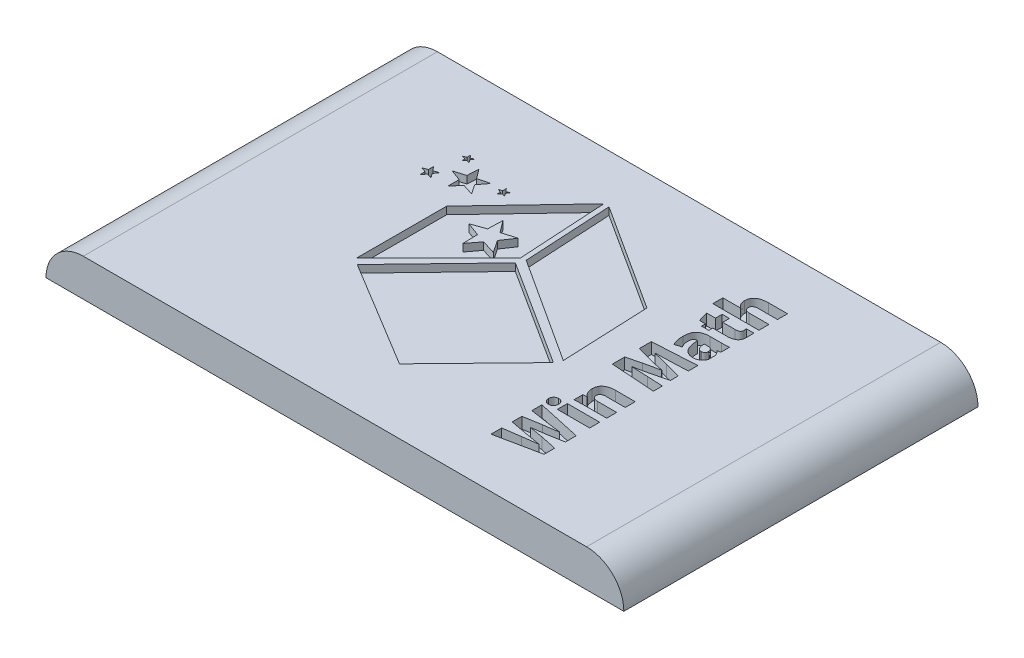
SolidWorks part; units mm, degrees
ref_plane "Front Plane" through (0, 0, 0) normal (0, 0, 1) x (1, 0, 0)
ref_plane "Top Plane" through (0, 0, 0) normal (0, 1, 0) x (1, 0, 0)
ref_plane "Right Plane" through (0, 0, 0) normal (1, 0, 0) x (0, 0, -1)
sketch "Sketch1" plane through (0, 0, 0) normal (0, 1, 0) x (1, 0, 0)
  line L1 (0, 0) -> (155, 0)
  line L2 (0, 0) -> (0, 95)
  line L3 (0, 95) -> (155, 95)
  line L4 (155, 0) -> (155, 95)
  dimension "D1" = 95
  dimension "D2" = 155
extrude "Boss-Extrude1" add sketch "Sketch1" along normal blind 10
fillet "Fillet1" radius 10 2 edges at (0, 10, -47.5) (155, 10, -47.5)
shell "Shell2" thickness 4 removed face at (77.5, 0, -47.5)
sketch "Sketch3" plane through (0, 10, 0) normal (0, 1, 0) x (1, 0, 0)
  line L0 (47.1109, 60.3769) -> (47.0833, 36.2437)
  line L1 (47.0833, 36.2437) -> (69.0367, 58.2599)
  line L2 (69.0367, 58.2599) -> (67.6381, 81.9832)
  line L3 (67.6381, 81.9832) -> (47.1109, 60.3769)
  line L4 (58.0076, 64.5969) -> (57.8826, 60.574)
  line L5 (57.8826, 60.574) -> (54.1743, 59.2566)
  line L6 (54.1743, 59.2566) -> (57.8661, 57.8917)
  line L7 (57.8661, 57.8917) -> (57.9418, 53.8673)
  line L8 (57.9418, 53.8673) -> (60.3485, 57.0467)
  line L9 (60.3485, 57.0467) -> (64.1037, 55.8769)
  line L10 (64.1037, 55.8769) -> (61.8991, 59.2068)
  line L11 (61.8991, 59.2068) -> (64.1443, 62.5081)
  line L12 (64.1443, 62.5081) -> (60.3751, 61.3868)
  line L13 (60.3751, 61.3868) -> (58.0076, 64.5969)
  line L14 (70.3473, 58.4621) -> (98.6174, 40.1514)
  line L15 (98.6174, 40.1514) -> (97.6168, 63.5776)
  line L16 (97.6168, 63.5776) -> (69.0367, 81.982)
  line L17 (69.0367, 81.982) -> (70.3473, 58.4621)
  line L18 (36.1479, 67.8344) -> (36.1422, 66.4292)
  line L19 (36.1422, 66.4292) -> (34.8275, 65.9323)
  line L20 (34.8275, 65.9323) -> (36.1624, 65.4928)
  line L21 (36.1624, 65.4928) -> (36.2285, 64.089)
  line L22 (36.2285, 64.089) -> (37.0591, 65.2226)
  line L23 (37.0591, 65.2226) -> (38.4147, 64.8518)
  line L24 (38.4147, 64.8518) -> (37.5931, 65.9921)
  line L25 (37.5931, 65.9921) -> (38.3648, 67.1665)
  line L26 (38.3648, 67.1665) -> (37.0264, 66.7376)
  line L27 (37.0264, 66.7376) -> (36.1479, 67.8344)
  line L28 (51.0281, 72.447) -> (51.027, 71.4893)
  line L29 (51.027, 71.4893) -> (50.1321, 71.148)
  line L30 (50.1321, 71.148) -> (51.0426, 70.8511)
  line L31 (51.0426, 70.8511) -> (51.0906, 69.8946)
  line L32 (51.0906, 69.8946) -> (51.6544, 70.6688)
  line L33 (51.6544, 70.6688) -> (52.5791, 70.4187)
  line L34 (52.5791, 70.4187) -> (52.0169, 71.1942)
  line L35 (52.0169, 71.1942) -> (52.5403, 71.9965)
  line L36 (52.5403, 71.9965) -> (51.6292, 71.7013)
  line L37 (51.6292, 71.7013) -> (51.0281, 72.447)
  line L38 (38.4638, 75.3981) -> (38.4901, 74.4758)
  line L39 (38.4901, 74.4758) -> (37.638, 74.1218)
  line L40 (37.638, 74.1218) -> (38.5233, 73.8618)
  line L41 (38.5233, 73.8618) -> (38.5967, 72.9421)
  line L42 (38.5967, 72.9421) -> (39.1174, 73.7036)
  line L43 (39.1174, 73.7036) -> (40.0149, 73.4891)
  line L44 (40.0149, 73.4891) -> (39.4515, 74.22)
  line L45 (39.4515, 74.22) -> (39.9328, 75.0072)
  line L46 (39.9328, 75.0072) -> (39.0638, 74.697)
  line L47 (39.0638, 74.697) -> (38.4638, 75.3981)
  line L48 (48.6785, 34.8084) -> (77.4183, 17.3974)
  line L49 (77.4183, 17.3974) -> (97.7621, 38.3361)
  line L50 (97.7621, 38.3361) -> (69.493, 56.4058)
  line L51 (69.493, 56.4058) -> (48.6785, 34.8084)
  line L52 (42.873, 73.2528) -> (42.6938, 70.2206)
  line L53 (42.6938, 70.2206) -> (39.6821, 69.2981)
  line L54 (39.6821, 69.2981) -> (42.6282, 68.1974)
  line L55 (42.6282, 68.1974) -> (42.6106, 65.1602)
  line L56 (42.6106, 65.1602) -> (44.6104, 67.5123)
  line L57 (44.6104, 67.5123) -> (47.6113, 66.5575)
  line L58 (47.6113, 66.5575) -> (45.9012, 69.1118)
  line L59 (45.9012, 69.1118) -> (47.7733, 71.5591)
  line L60 (47.7733, 71.5591) -> (44.7165, 70.7858)
  line L61 (44.7165, 70.7858) -> (42.873, 73.2528)
  spline S0 degree 3 poles (112.3162, 74.0035) (112.3162, 73.439) (112.3162, 72.8745) (112.3162, 72.31) knots 18 18 18 18 19 19 19 19
  spline S1 degree 3 poles (112.1249, 74.3129) (112.1938, 74.2134) (112.2528, 74.1068) (112.3162, 74.0035) knots 17 17 17 17 18 18 18 18
  spline S2 degree 3 poles (110.5374, 73.9138) (110.5459, 74.1404) (110.1829, 74.5507) (110.6633, 74.5671) (111.1436, 74.5834) (111.7302, 74.8835) (112.1249, 74.3129) knots 15 15 15 15 16 16 16 17 17 17 17
  spline S3 degree 3 poles (109.4304, 72.9149) (110.0624, 72.9344) (110.51, 73.187) (110.5374, 73.9138) knots 14 14 14 14 15 15 15 15
  spline S4 degree 3 poles (107.1794, 72.8956) (107.9262, 72.9505) (108.6805, 72.8917) (109.4304, 72.9149) knots 13 13 13 13 14 14 14 14
  spline S5 degree 3 poles (106.2942, 73.7451) (106.1518, 73.0011) (106.5134, 72.8465) (107.1794, 72.8956) knots 12 12 12 12 13 13 13 13
  spline S6 degree 3 poles (105.4432, 74.632) (106.1481, 74.6264) (106.4274, 74.442) (106.2942, 73.7451) knots 11 11 11 11 12 12 12 12
  spline S7 degree 3 poles (104.6003, 73.7348) (104.4834, 74.4138) (104.7173, 74.6378) (105.4432, 74.632) knots 10 10 10 10 11 11 11 11
  spline S8 degree 3 poles (103.8002, 72.8978) (104.4815, 72.8168) (104.7098, 73.0998) (104.6003, 73.7348) knots 9 9 9 9 10 10 10 10
  spline S9 degree 3 poles (102.3025, 72.9083) (102.8712, 72.9083) (103.3417, 72.9524) (103.8002, 72.8978) knots 8 8 8 8 9 9 9 9
  spline S10 degree 3 poles (102.6278, 71.762) (102.5888, 72.1199) (102.4324, 72.465) (102.3025, 72.9083) knots 7 7 7 7 8 8 8 8
  spline S11 degree 3 poles (104.0804, 70.6118) (103.1368, 70.4326) (102.7255, 70.8623) (102.6278, 71.762) knots 6 6 6 6 7 7 7 7
  spline S12 degree 3 poles (104.5957, 69.9056) (104.6247, 70.2676) (104.7022, 70.73) (104.0804, 70.6118) knots 5 5 5 5 6 6 6 6
  spline S13 degree 3 poles (105.162, 69.4172) (104.8053, 69.3444) (104.5596, 69.4567) (104.5957, 69.9056) knots 4 4 4 4 5 5 5 5
  spline S14 degree 3 poles (106.239, 69.7092) (106.2741, 69.1592) (105.5409, 69.4947) (105.162, 69.4172) knots 3 3 3 3 4 4 4 4
  spline S15 degree 3 poles (107.4693, 70.6148) (106.8556, 70.6087) (106.1666, 70.843) (106.239, 69.7092) knots 2 2 2 2 3 3 3 3
  spline S16 degree 3 poles (109.6276, 70.6122) (108.9089, 70.6355) (108.1888, 70.6217) (107.4693, 70.6148) knots 1 1 1 1 2 2 2 2
  spline S17 degree 3 poles (112.3162, 72.31) (111.8721, 71.028) (110.9158, 70.5701) (109.6276, 70.6122) knots 0 0 0 0 1 1 1 1
  spline S18 degree 3 poles (101.0336, 30.8311) (101.012, 31.0115) (101.0121, 31.3775) (101.0336, 31.5579) knots 4 4 4 4 5 5 5 5
  spline S19 degree 3 poles (102.4218, 29.9289) (101.7033, 29.7892) (101.1233, 30.0827) (101.0336, 30.8311) knots 3 3 3 3 4 4 4 4
  spline S20 degree 3 poles (103.3567, 31.1524) (103.3501, 30.5233) (103.0596, 30.0529) (102.4218, 29.9289) knots 2 2 2 2 3 3 3 3
  spline S21 degree 3 poles (102.4225, 32.4638) (103.1294, 32.3367) (103.3635, 31.8052) (103.3567, 31.1524) knots 1 1 1 1 2 2 2 2
  spline S22 degree 3 poles (101.0336, 31.5579) (101.1228, 32.3078) (101.7049, 32.5929) (102.4225, 32.4638) knots 0 0 0 0 1 1 1 1
  spline S23 degree 3 poles (103.3839, 17.0908) (105.4024, 17.5283) (107.4247, 17.9477) (109.4253, 18.3708) knots 17 17 17 17 18 18 18 18
  spline S24 degree 3 poles (101.579, 14.8015) (101.5551, 16.6817) (101.5349, 16.6901) (103.3839, 17.0908) knots 16 16 16 16 17 17 17 17
  spline S25 degree 3 poles (102.2542, 14.2833) (101.6623, 14.1186) (101.5858, 14.2574) (101.579, 14.8015) knots 15 15 15 15 16 16 16 16
  spline S26 degree 3 poles (110.2388, 16.3991) (107.5763, 15.6969) (104.9066, 15.0215) (102.2542, 14.2833) knots 14 14 14 14 15 15 15 15
  spline S27 degree 3 poles (112.1448, 18.8638) (112.1183, 16.9059) (112.1481, 16.9027) (110.2388, 16.3991) knots 13 13 13 13 14 14 14 14
  spline S28 degree 3 poles (111.3476, 19.8495) (111.9397, 19.7038) (112.1534, 19.4935) (112.1448, 18.8638) knots 12 12 12 12 13 13 13 13
  spline S29 degree 3 poles (104.6287, 21.6224) (106.9397, 21.0063) (109.1351, 20.3936) (111.3476, 19.8495) knots 11 11 11 11 12 12 12 12
  spline S30 degree 3 poles (110.2772, 23.0869) (108.4322, 22.6042) (106.5854, 22.1294) (104.6287, 21.6224) knots 10 10 10 10 11 11 11 11
  spline S31 degree 3 poles (112.1398, 25.6724) (112.2343, 23.6052) (112.2479, 23.6025) (110.2772, 23.0869) knots 9 9 9 9 10 10 10 10
  spline S32 degree 3 poles (111.6626, 26.3302) (112.0283, 26.2348) (112.1229, 26.0446) (112.1398, 25.6724) knots 8 8 8 8 9 9 9 9
  spline S33 degree 3 poles (101.5904, 28.9765) (105.011, 28.0762) (108.3354, 27.1977) (111.6626, 26.3302) knots 7 7 7 7 8 8 8 8
  spline S34 degree 3 poles (101.58, 27.6056) (101.6395, 28.0284) (101.5904, 28.4665) (101.5904, 28.9765) knots 6 6 6 6 7 7 7 7
  spline S35 degree 3 poles (102.5993, 26.3575) (101.7769, 26.4996) (101.4647, 26.7878) (101.58, 27.6056) knots 5 5 5 5 6 6 6 6
  spline S36 degree 3 poles (109.4363, 24.9636) (107.0496, 25.4595) (104.8353, 25.971) (102.5993, 26.3575) knots 4 4 4 4 5 5 5 5
  spline S37 degree 3 poles (103.4359, 23.5078) (105.3818, 23.9769) (107.3264, 24.4514) (109.4363, 24.9636) knots 3 3 3 3 4 4 4 4
  spline S38 degree 3 poles (101.5805, 21.0141) (101.4585, 23.0314) (101.4478, 23.0285) (103.4359, 23.5078) knots 2 2 2 2 3 3 3 3
  spline S39 degree 3 poles (102.0765, 20.3639) (101.7, 20.4638) (101.6029, 20.6435) (101.5805, 21.0141) knots 1 1 1 1 2 2 2 2
  spline S40 degree 3 poles (109.4253, 18.3708) (106.9688, 19.0401) (104.5258, 19.7142) (102.0765, 20.3639) knots 0 0 0 0 1 1 1 1
  spline S41 degree 3 poles (104.1541, 50.0484) (104.4099, 50.1937) (104.807, 50.0704) (105.1942, 50.0781) knots 23 23 23 23 24 24 24 24
  spline S42 degree 3 poles (104.6284, 50.2523) (104.4306, 50.188) (104.2333, 50.0814) (104.1541, 50.0484) knots 22 22 22 22 23 23 23 23
  spline S43 degree 3 poles (111.4571, 52.606) (109.1638, 51.8748) (106.9022, 51.0442) (104.6284, 50.2523) knots 21 21 21 21 22 22 22 22
  spline S44 degree 3 poles (112.1332, 53.9092) (112.1102, 53.3632) (112.2355, 52.8542) (111.4571, 52.606) knots 20 20 20 20 21 21 21 21
  spline S45 degree 3 poles (111.4136, 55.072) (112.1488, 54.9063) (112.1567, 54.4708) (112.1332, 53.9092) knots 19 19 19 19 20 20 20 20
  spline S46 degree 3 poles (108.8369, 55.9454) (109.6941, 55.6467) (110.5339, 55.2705) (111.4136, 55.072) knots 18 18 18 18 19 19 19 19
  spline S47 degree 3 poles (104.6493, 57.4043) (106.0452, 56.9181) (107.4412, 56.4319) (108.8369, 55.9454) knots 17 17 17 17 18 18 18 18
  spline S48 degree 3 poles (104.6883, 57.5987) (104.6754, 57.5341) (104.6624, 57.4692) (104.6493, 57.4043) knots 16 16 16 16 17 17 17 17
  spline S49 degree 3 poles (112.1442, 59.0497) (112.0997, 57.6) (112.1363, 57.5987) (110.6425, 57.5987) (108.6577, 57.5987) (106.6731, 57.5987) (104.6883, 57.5987) knots 14 14 14 14 15 15 15 16 16 16 16
  spline S50 degree 3 poles (111.2873, 59.9443) (112.0244, 59.9612) (112.165, 59.7245) (112.1442, 59.0497) knots 13 13 13 13 14 14 14 14
  spline S51 degree 3 poles (104.2342, 59.9145) (106.5851, 59.943) (108.9374, 59.8903) (111.2873, 59.9443) knots 12 12 12 12 13 13 13 13
  spline S52 degree 3 poles (101.7295, 59.733) (102.2215, 60.3085) (103.372, 59.904) (104.2342, 59.9145) knots 11 11 11 11 12 12 12 12
  spline S53 degree 3 poles (101.5783, 57.2807) (101.6437, 58.1186) (101.3062, 59.2375) (101.7295, 59.733) knots 10 10 10 10 11 11 11 11
  spline S54 degree 3 poles (102.2759, 56.2896) (101.7475, 56.4642) (101.5338, 56.7115) (101.5783, 57.2807) knots 9 9 9 9 10 10 10 10
  spline S55 degree 3 poles (109.093, 53.9639) (106.8433, 54.7357) (104.5664, 55.5333) (102.2759, 56.2896) knots 8 8 8 8 9 9 9 9
  spline S56 degree 3 poles (104.0484, 52.2386) (105.733, 52.8204) (107.4206, 53.3926) (109.093, 53.9639) knots 7 7 7 7 8 8 8 8
  spline S57 degree 3 poles (101.7385, 51.3251) (102.1888, 51.8865) (103.2509, 51.9632) (104.0484, 52.2386) knots 6 6 6 6 7 7 7 7
  spline S58 degree 3 poles (101.5805, 48.7731) (101.6626, 49.6393) (101.2518, 50.718) (101.7385, 51.3251) knots 5 5 5 5 6 6 6 6
  spline S59 degree 3 poles (102.4023, 47.9412) (101.7409, 47.9324) (101.518, 48.1149) (101.5805, 48.7731) knots 4 4 4 4 5 5 5 5
  spline S60 degree 3 poles (110.8665, 47.957) (108.0451, 47.957) (105.2232, 47.9785) (102.4023, 47.9412) knots 3 3 3 3 4 4 4 4
  spline S61 degree 3 poles (112.145, 49.2617) (112.1034, 47.9585) (112.144, 47.9571) (110.8665, 47.957) knots 2 2 2 2 3 3 3 3
  spline S62 degree 3 poles (111.307, 50.0877) (111.9605, 50.1009) (112.1663, 49.9308) (112.145, 49.2617) knots 1 1 1 1 2 2 2 2
  spline S63 degree 3 poles (105.1942, 50.0781) (107.2319, 50.0763) (109.2702, 50.0471) (111.307, 50.0877) knots 0 0 0 0 1 1 1 1
  spline S64 degree 3 poles (104.4141, 80.8549) (104.5146, 82.1147) (105.1697, 82.7689) (106.654, 83.0604) knots 14 14 14 14 15 15 15 15
  spline S65 degree 3 poles (105.3518, 78.5159) (104.6971, 79.1584) (104.3391, 79.9144) (104.4141, 80.8549) knots 13 13 13 13 14 14 14 14
  spline S66 degree 3 poles (105.3182, 78.1874) (105.7407, 78.2069) (105.6135, 78.3763) (105.3518, 78.5159) knots 12 12 12 12 13 13 13 13
  spline S67 degree 3 poles (101.0733, 75.9216) (100.8796, 78.1775) (100.8796, 78.1775) (103.0861, 78.1775) (103.8303, 78.1775) (104.5756, 78.153) (105.3182, 78.1874) knots 10 10 10 10 11 11 11 12 12 12 12
  spline S68 degree 3 poles (111.3175, 75.9029) (107.903, 75.9381) (104.4882, 75.9207) (101.0733, 75.9216) knots 9 9 9 9 10 10 10 10
  spline S69 degree 3 poles (112.1332, 76.7386) (112.2306, 76.0861) (111.9831, 75.8959) (111.3175, 75.9029) knots 8 8 8 8 9 9 9 9
  spline S70 degree 3 poles (112.1332, 77.395) (112.1018, 77.1804) (112.1012, 76.9532) (112.1332, 76.7386) knots 7 7 7 7 8 8 8 8
  spline S71 degree 3 poles (111.3287, 78.2416) (112.0082, 78.2535) (112.2262, 78.0334) (112.1332, 77.395) knots 6 6 6 6 7 7 7 7
  spline S72 degree 3 poles (107.3892, 78.3046) (108.6961, 78.1117) (110.0166, 78.2186) (111.3287, 78.2416) knots 5 5 5 5 6 6 6 6
  spline S73 degree 3 poles (106.215, 79.7438) (106.1609, 78.9437) (106.5922, 78.4224) (107.3892, 78.3046) knots 4 4 4 4 5 5 5 5
  spline S74 degree 3 poles (107.5362, 80.7968) (106.8534, 80.7727) (106.2673, 80.5215) (106.215, 79.7438) knots 3 3 3 3 4 4 4 4
  spline S75 degree 3 poles (109.9793, 80.8108) (109.1649, 80.8104) (108.3497, 80.8255) (107.5362, 80.7968) knots 2 2 2 2 3 3 3 3
  spline S76 degree 3 poles (112.1062, 83.0159) (112.1874, 80.8111) (112.1874, 80.8119) (109.9793, 80.8108) knots 1 1 1 1 2 2 2 2
  spline S77 degree 3 poles (106.654, 83.0604) (108.4714, 83.0457) (110.2888, 83.0308) (112.1062, 83.0159) knots 0 0 0 0 1 1 1 1
  spline S78 degree 3 poles (104.6008, 35.602) (104.5942, 36.2331) (104.4158, 37.0061) (105.678, 36.6475) knots 14 14 14 14 15 15 15 15
  spline S79 degree 3 poles (104.5966, 35.0382) (104.6254, 35.2218) (104.6026, 35.4138) (104.6008, 35.602) knots 13 13 13 13 14 14 14 14
  spline S80 degree 3 poles (105.3395, 34.3205) (104.7827, 34.3099) (104.5016, 34.4317) (104.5966, 35.0382) knots 12 12 12 12 13 13 13 13
  spline S81 degree 3 poles (112.1418, 35.8544) (112.1233, 34.333) (112.1505, 34.3327) (110.6078, 34.3327) (108.8516, 34.3327) (107.095, 34.3538) (105.3395, 34.3205) knots 10 10 10 10 11 11 11 12 12 12 12
  spline S82 degree 3 poles (111.3765, 36.6519) (112.0205, 36.6779) (112.149, 36.4437) (112.1418, 35.8544) knots 9 9 9 9 10 10 10 10
  spline S83 degree 3 poles (107.7091, 36.6628) (108.9297, 36.6066) (110.1557, 36.6026) (111.3765, 36.6519) knots 8 8 8 8 9 9 9 9
  spline S84 degree 3 poles (106.1999, 38.0294) (106.1821, 37.2943) (106.7898, 36.7052) (107.7091, 36.6628) knots 7 7 7 7 8 8 8 8
  spline S85 degree 3 poles (107.6693, 39.2727) (106.8997, 39.2311) (106.2229, 38.9732) (106.1999, 38.0294) knots 6 6 6 6 7 7 7 7
  spline S86 degree 3 poles (110.4904, 39.3001) (109.5497, 39.2987) (108.6074, 39.3235) (107.6693, 39.2727) knots 5 5 5 5 6 6 6 6
  spline S87 degree 3 poles (112.1363, 41.1729) (112.371, 39.4291) (112.2679, 39.3028) (110.4904, 39.3001) knots 4 4 4 4 5 5 5 5
  spline S88 degree 3 poles (111.6822, 41.6063) (112.0025, 41.6176) (112.094, 41.4859) (112.1363, 41.1729) knots 3 3 3 3 4 4 4 4
  spline S89 degree 3 poles (106.4245, 41.4787) (108.1671, 41.7607) (109.9297, 41.5443) (111.6822, 41.6063) knots 2 2 2 2 3 3 3 3
  spline S90 degree 3 poles (104.4599, 38.5103) (104.1324, 40.0226) (104.9022, 41.2325) (106.4245, 41.4787) knots 1 1 1 1 2 2 2 2
  spline S91 degree 3 poles (105.678, 36.6475) (104.9821, 37.2484) (104.6115, 37.8094) (104.4599, 38.5103) knots 0 0 0 0 1 1 1 1
  spline S92 degree 3 poles (106.1093, 32.3089) (106.8609, 32.3089) (107.6127, 32.3089) (108.3642, 32.3088) knots 6 6 6 6 7 7 7 7
  spline S93 degree 3 poles (104.5857, 30.7828) (104.6074, 32.3084) (104.5771, 32.3088) (106.1093, 32.3089) knots 5 5 5 5 6 6 6 6
  spline S94 degree 3 poles (105.3586, 29.9894) (104.725, 29.9733) (104.5773, 30.1792) (104.5857, 30.7828) knots 4 4 4 4 5 5 5 5
  spline S95 degree 3 poles (112.1415, 31.6289) (112.1556, 30.0042) (112.178, 30.0044) (110.526, 30.0044) (108.8034, 30.0044) (107.0801, 30.0332) (105.3586, 29.9894) knots 2 2 2 2 3 3 3 4 4 4 4
  spline S96 degree 3 poles (111.4645, 32.3203) (112.0101, 32.3418) (112.1369, 32.1477) (112.1415, 31.6289) knots 1 1 1 1 2 2 2 2
  spline S97 degree 3 poles (108.3642, 32.3088) (109.3979, 32.3086) (110.4325, 32.2798) (111.4645, 32.3203) knots 0 0 0 0 1 1 1 1
  spline S98 degree 3 poles (111.4373, 68.2591) (110.1234, 68.2286) (108.8078, 68.2683) (107.4936, 68.2444) knots 15 15 15 15 16 16 16 16
  spline S99 degree 3 poles (112.133, 67.5965) (112.2113, 68.158) (111.9445, 68.2711) (111.4373, 68.2591) knots 14 14 14 14 15 15 15 15
  spline S100 degree 3 poles (112.1301, 66.9401) (112.1181, 67.1584) (112.1029, 67.3817) (112.133, 67.5965) knots 13 13 13 13 14 14 14 14
  spline S101 degree 3 poles (111.1942, 66.0808) (112.2251, 65.7883) (112.1611, 66.3737) (112.1301, 66.9401) knots 12 12 12 12 13 13 13 13
  spline S102 degree 3 poles (112.3162, 64.5949) (111.9853, 65.0617) (111.7247, 65.5775) (111.1942, 66.0808) knots 11 11 11 11 12 12 12 12
  spline S103 degree 3 poles (112.3162, 63.0895) (112.3162, 63.5912) (112.3162, 64.0932) (112.3162, 64.5949) knots 10 10 10 10 11 11 11 11
  spline S104 degree 3 poles (109.6901, 61.4519) (110.8719, 61.2935) (111.64, 61.7723) (112.3162, 63.0895) knots 9 9 9 9 10 10 10 10
  spline S105 degree 3 poles (107.5555, 63.8176) (107.8334, 62.3093) (108.4666, 61.6158) (109.6901, 61.4519) knots 8 8 8 8 9 9 9 9
  spline S106 degree 3 poles (107.2955, 65.4852) (107.3993, 64.9327) (107.4537, 64.3707) (107.5555, 63.8176) knots 7 7 7 7 8 8 8 8
  spline S107 degree 3 poles (107.0656, 66.0385) (107.3453, 65.9728) (107.2591, 65.6795) (107.2955, 65.4852) knots 6 6 6 6 7 7 7 7
  spline S108 degree 3 poles (106.3903, 65.7822) (106.574, 65.9588) (106.8089, 66.0992) (107.0656, 66.0385) knots 5 5 5 5 6 6 6 6
  spline S109 degree 3 poles (106.0189, 64.3847) (105.9906, 64.8915) (105.9875, 65.3954) (106.3903, 65.7822) knots 4 4 4 4 5 5 5 5
  spline S110 degree 3 poles (106.6826, 62.2613) (106.4259, 62.9661) (106.0608, 63.6298) (106.0189, 64.3847) knots 3 3 3 3 4 4 4 4
  spline S111 degree 3 poles (104.5868, 63.6662) (104.8915, 62.0965) (104.9568, 62.0586) (106.6826, 62.2613) knots 2 2 2 2 3 3 3 3
  spline S112 degree 3 poles (104.4205, 65.0595) (104.4246, 64.5942) (104.4979, 64.1247) (104.5868, 63.6662) knots 1 1 1 1 2 2 2 2
  spline S113 degree 3 poles (107.4936, 68.2444) (105.4358, 68.2069) (104.4029, 67.1349) (104.4205, 65.0595) knots 0 0 0 0 1 1 1 1
  spline S114 degree 3 poles (108.9846, 66.0792) (109.8452, 66.1209) (110.6122, 65.513) (110.6554, 64.6919) knots 3 3 3 3 4 4 4 4
  spline S115 degree 3 poles (108.6052, 65.5365) (108.5486, 65.8447) (108.5517, 66.058) (108.9846, 66.0792) knots 2 2 2 2 3 3 3 3
  spline S116 degree 3 poles (109.8132, 63.5703) (109.076, 63.4828) (108.6888, 64.1318) (108.6052, 65.5365) knots 1 1 1 1 2 2 2 2
  spline S117 degree 3 poles (110.6554, 64.6919) (110.6875, 64.0804) (110.4584, 63.6467) (109.8132, 63.5703) knots 0 0 0 0 1 1 1 1
extrude "Cut-Extrude2" cut sketch "Sketch3" against normal blind 2 contours L2 L3 L0 L1 L13 L12 L11 L10 L9 L8 L7 L6 L5 L4 | L50 L51 L48 L49 | L16 L17 L14 L15 | L26 L27 L18 L19 L20 L21 L22 L23 L24 L25 | L46 L47 L38 L39 L40 L41 L42 L43 L44 L45 | L60 L61 L52 L53 L54 L55 L56 L57 L58 L59 | L36 L37 L28 L29 L30 L31 L32 L33 L34 L35 region at (57.7423, 10, -70.8306) region at (83.9146, 10, -61.0578) region at (36.7966, 10, -65.9748) region at (51.474, 10, -71.181) region at (38.9292, 10, -74.1916) region at (73.2779, 10, -36.7846) region at (44.1101, 10, -69.1656)
sketch "Sketch10" plane through (0, 10, 0) normal (0, 1, 0) x (1, 0, 0)
  line L0 (110.1325, 76.1337) -> (110.1345, 76.1026)
  line L1 (10, 0) -> (145, 0) construction
  line L2 (117.8303, 95) -> (117.8303, 0)
  line L3 (145, 95) -> (10, 95) construction
  line L4 (110.1345, 76.1026) -> (105.4552, 76.1026)
  line L5 (105.4552, 76.1026) -> (105.4552, 73.4158)
  line L6 (105.4552, 73.4158) -> (117.8214, 73.4158)
  line L7 (117.8214, 73.4158) -> (117.8214, 76.1026)
  line L8 (117.8214, 76.1026) -> (112.5347, 76.1026)
  line L9 (112.8304, 78.3957) -> (117.8214, 78.3979)
  line L10 (117.8214, 78.3979) -> (117.8214, 81.0847)
  line L11 (117.8214, 81.0847) -> (112.7429, 81.0847)
  line L12 (109.1674, 67.7279) -> (109.1674, 66.6671)
  line L13 (109.1674, 66.6671) -> (111.1199, 66.6671)
  line L14 (111.1199, 66.6671) -> (111.1199, 67.7279)
  line L15 (111.1199, 67.7279) -> (114.7821, 67.7279)
  line L16 (117.7725, 72.0924) -> (115.7681, 72.0786)
  line L17 (114.4363, 70.4021) -> (111.1199, 70.4029)
  line L18 (111.1199, 70.4029) -> (111.1199, 72.2016)
  line L19 (111.1199, 72.2016) -> (109.1674, 72.2016)
  line L20 (109.1674, 72.2016) -> (109.1674, 70.4029)
  line L21 (109.1674, 70.4029) -> (106.8307, 70.4029)
  line L22 (106.8307, 70.4029) -> (107.584, 67.7279)
  line L23 (107.584, 67.7279) -> (109.1674, 67.7279)
  line L24 (109.7211, 58.752) -> (111.4404, 59.2325)
  line L25 (116.9362, 63.0157) -> (116.9373, 63.0608)
  line L26 (116.9373, 63.0608) -> (117.8214, 63.2096)
  line L27 (117.8214, 63.2096) -> (117.8214, 65.565)
  line L28 (115.7552, 65.4244) -> (112.6946, 65.4266)
  line L29 (113.6934, 62.88) -> (114.8022, 62.8822)
  line L30 (106.0245, 56.3471) -> (106.0245, 53.0879)
  line L31 (106.0245, 53.0879) -> (109.8249, 52.0733)
  line L32 (114.0671, 51.1343) -> (114.0673, 51.074)
  line L33 (109.839, 50.1668) -> (106.0245, 49.2138)
  line L34 (106.0245, 49.2138) -> (106.0245, 45.9085)
  line L35 (106.0245, 45.9085) -> (117.8214, 45.0937)
  line L36 (117.8214, 45.0937) -> (117.8214, 47.5227)
  line L37 (117.8214, 47.5227) -> (113.6248, 47.7226)
  line L38 (109.2674, 47.907) -> (109.2674, 47.9532)
  line L39 (113.4287, 48.8278) -> (117.6087, 49.8902)
  line L40 (117.6087, 49.8902) -> (117.6087, 51.9349)
  line L41 (117.6087, 51.9349) -> (113.4002, 53.1033)
  line L42 (109.2674, 54.148) -> (109.2674, 54.1948)
  line L43 (113.6267, 54.3014) -> (117.8214, 54.4716)
  line L44 (117.8214, 54.4716) -> (117.8214, 57.0236)
  line L45 (117.8214, 57.0236) -> (106.0245, 56.3471)
  line L46 (110.2104, 34.9892) -> (110.2112, 34.9439)
  line L47 (110.2112, 34.9439) -> (109.1561, 34.8066)
  line L48 (109.1561, 34.8066) -> (109.1561, 32.5011)
  line L49 (111.9252, 32.5604) -> (117.8214, 32.5626)
  line L50 (117.8214, 32.5626) -> (117.8214, 35.2494)
  line L51 (117.8214, 35.2494) -> (112.675, 35.2494)
  line L52 (112.7215, 37.5425) -> (117.8214, 37.5447)
  line L53 (117.8214, 37.5447) -> (117.8214, 40.2315)
  line L54 (117.8214, 40.2315) -> (112.5423, 40.2315)
  line L55 (106.8052, 30.7232) -> (106.806, 30.7251)
  line L56 (109.1561, 30.6943) -> (109.1561, 28.0076)
  line L57 (109.1561, 28.0076) -> (117.8214, 28.0076)
  line L58 (117.8214, 28.0076) -> (117.8214, 30.6943)
  line L59 (117.8214, 30.6943) -> (109.1561, 30.6943)
  line L60 (106.0245, 24.2977) -> (110.6032, 23.5931)
  line L61 (114.7388, 23.041) -> (114.7388, 22.9957)
  line L62 (110.693, 22.4272) -> (106.0245, 21.6325)
  line L63 (106.0245, 21.6325) -> (106.0245, 19.0286)
  line L64 (106.0245, 19.0286) -> (110.6032, 18.1708)
  line L65 (114.7677, 17.4495) -> (114.7693, 17.4203)
  line L66 (110.633, 16.8824) -> (106.0245, 16.2103)
  line L67 (106.0245, 16.2103) -> (106.0245, 13.346)
  line L68 (106.0245, 13.346) -> (117.8214, 15.7814)
  line L69 (117.8214, 15.7814) -> (117.8214, 18.6304)
  line L70 (117.8214, 18.6304) -> (113.5332, 19.5341)
  line L71 (109.7923, 20.1763) -> (109.7943, 20.208)
  line L72 (113.5177, 20.7279) -> (117.8214, 21.5253)
  line L73 (117.8214, 21.5253) -> (117.8214, 24.4049)
  line L74 (117.8214, 24.4049) -> (106.0245, 26.9933)
  line L75 (106.0245, 26.9933) -> (106.0245, 24.2977)
  spline S0 degree 3 poles (112.7429, 81.0847) (112.4587, 81.0827) (112.0449, 81.0621) (111.5137, 80.9902) (111.1544, 80.9153) (110.8216, 80.8168) (110.5143, 80.7004) (110.2332, 80.5615) (109.9791, 80.402) (109.7527, 80.221) (109.5549, 80.0203) (109.3897, 79.7979) (109.2524, 79.5577) (109.1452, 79.2985) (109.0425, 78.9175) (109.013, 78.6165) (109.0138, 78.4112) knots 0 0 0 0 0.164293 0.239153 0.309681 0.376271 0.439631 0.499436 0.557227 0.612718 0.666669 0.719645 0.772435 0.826243 0.881352 1 1 1 1
  spline S1 degree 3 poles (109.0138, 78.4112) (109.0077, 78.2237) (109.0384, 77.9371) (109.1353, 77.5572) (109.2418, 77.261) (109.3872, 76.9623) (109.6672, 76.5648) (109.9335, 76.2984) (110.1325, 76.1337) knots 0 0 0 0 0.213675 0.327186 0.446851 0.572508 0.705145 1 1 1 1
  spline S2 degree 3 poles (112.5347, 76.1026) (112.397, 76.1058) (112.2015, 76.1313) (111.9539, 76.1788) (111.7992, 76.2357) (111.6601, 76.2945) (111.543, 76.3717) (111.4451, 76.4593) (111.3456, 76.5876) (111.2539, 76.7512) (111.1528, 76.9884) (111.1214, 77.1688) (111.1312, 77.2814) knots 0 0 0 0 0.199073 0.285917 0.364428 0.437538 0.504307 0.566694 0.627116 0.738822 0.837611 1 1 1 1
  spline S3 degree 3 poles (111.1312, 77.2814) (111.1343, 77.377) (111.1493, 77.5163) (111.2014, 77.6908) (111.2545, 77.8061) (111.3221, 77.9108) (111.4056, 78.0022) (111.502, 78.0831) (111.652, 78.1763) (111.8678, 78.2692) (112.2738, 78.3761) (112.6025, 78.401) (112.8304, 78.3957) knots 0 0 0 0 0.124913 0.181513 0.236902 0.290015 0.343427 0.397664 0.453741 0.573248 0.702519 1 1 1 1
  spline S4 degree 3 poles (114.7821, 67.7279) (114.9295, 67.713) (115.1563, 67.711) (115.4632, 67.738) (115.7056, 67.7729) (115.9554, 67.8279) (116.2131, 67.8963) (116.4782, 67.9826) (116.7494, 68.0777) (117.0152, 68.2032) (117.2466, 68.3902) (117.4497, 68.6168) (117.6172, 68.8929) (117.7545, 69.2125) (117.8988, 69.7264) (117.9473, 70.1427) (117.9638, 70.4332) knots 0 0 0 0 0.092257 0.14094 0.191834 0.244748 0.300216 0.357924 0.418428 0.479374 0.539907 0.602401 0.668166 0.740168 0.818535 1 1 1 1
  spline S5 degree 3 poles (117.9638, 70.4332) (117.9638, 70.6077) (117.9493, 70.8604) (117.9306, 71.1853) (117.9075, 71.4018) (117.8813, 71.5999) (117.842, 71.8296) (117.8037, 71.9917) (117.7725, 72.0924) knots 0 0 0 0 0.312293 0.453346 0.582825 0.702068 0.811215 1 1 1 1
  spline S6 degree 3 poles (115.7681, 72.0786) (115.799, 71.9719) (115.8377, 71.736) (115.847, 71.4973) (115.8464, 71.3696) knots 0 0 0 0 0.464501 1 1 1 1
  spline S7 degree 3 poles (115.8464, 71.3696) (115.8477, 71.2268) (115.8194, 71.0127) (115.6774, 70.7738) (115.5278, 70.6334) (115.33, 70.524) (114.9638, 70.4199) (114.6556, 70.4042) (114.4363, 70.4021) knots 0 0 0 0 0.220467 0.319826 0.420264 0.531156 0.663034 1 1 1 1
  spline S8 degree 3 poles (112.6946, 65.4266) (112.4525, 65.4342) (112.0957, 65.4185) (111.6311, 65.3547) (111.3032, 65.2768) (110.9865, 65.1813) (110.6849, 65.0551) (110.3972, 64.9053) (110.1217, 64.7335) (109.8671, 64.5273) (109.647, 64.2755) (109.4587, 63.9834) (109.3067, 63.6474) (109.1815, 63.2721) (109.058, 62.6905) (109.0193, 62.2283) (109.0138, 61.908) knots 0 0 0 0 0.124012 0.182749 0.240082 0.296572 0.352109 0.407345 0.462689 0.518301 0.574566 0.63338 0.695775 0.763066 0.835813 1 1 1 1
  spline S9 degree 3 poles (109.0138, 61.908) (109.0157, 61.5534) (109.049, 61.0423) (109.1475, 60.3929) (109.2487, 59.972) (109.3621, 59.5981) (109.5058, 59.1903) (109.6288, 58.9144) (109.7211, 58.752) knots 0 0 0 0 0.325721 0.469837 0.602829 0.723065 0.828626 1 1 1 1
  spline S10 degree 3 poles (111.4404, 59.2325) (111.3459, 59.3709) (111.2308, 59.6001) (111.0954, 59.9212) (111.0099, 60.184) (110.9376, 60.4592) (110.8704, 60.8482) (110.8446, 61.1471) (110.8465, 61.3498) knots 0 0 0 0 0.224854 0.344805 0.468872 0.596717 0.72753 1 1 1 1
  spline S11 degree 3 poles (110.8465, 61.3498) (110.845, 61.4787) (110.8612, 61.6627) (110.8911, 61.8979) (110.9312, 62.0486) (110.973, 62.1856) (111.0299, 62.3044) (111.0934, 62.408) (111.1927, 62.5213) (111.3385, 62.6329) (111.6129, 62.7638) (111.8465, 62.7914) (112.0031, 62.7844) knots 0 0 0 0 0.181809 0.261271 0.334749 0.402043 0.463473 0.520477 0.573236 0.675566 0.777783 1 1 1 1
  spline S12 degree 3 poles (112.0031, 62.7844) (112.0059, 62.466) (112.0237, 61.997) (112.1086, 61.3911) (112.195, 60.969) (112.3063, 60.5698) (112.4409, 60.1919) (112.6051, 59.8385) (112.7866, 59.5051) (113.0002, 59.2046) (113.2412, 58.9379) (113.5159, 58.7141) (113.8184, 58.5287) (114.149, 58.3796) (114.6432, 58.2356) (115.0367, 58.1895) (115.3059, 58.1826) knots 0 0 0 0 0.149723 0.220091 0.287334 0.352093 0.414698 0.47566 0.53509 0.59281 0.648548 0.703514 0.758732 0.814879 0.873418 1 1 1 1
  spline S13 degree 3 poles (115.3059, 58.1826) (115.4835, 58.1827) (115.7455, 58.2088) (116.084, 58.2823) (116.322, 58.3618) (116.5511, 58.4564) (116.767, 58.5757) (116.9735, 58.7136) (117.1647, 58.8741) (117.3448, 59.0474) (117.4969, 59.2437) (117.6329, 59.4503) (117.741, 59.6746) (117.8292, 59.9127) (117.9156, 60.2581) (117.9451, 60.5292) (117.9504, 60.7137) knots 0 0 0 0 0.130267 0.192751 0.254049 0.31432 0.374506 0.434912 0.496401 0.557619 0.61808 0.678342 0.738976 0.800475 0.864523 1 1 1 1
  spline S14 degree 3 poles (117.9504, 60.7137) (117.9547, 60.9399) (117.9212, 61.2744) (117.8212, 61.7064) (117.7114, 62.0111) (117.5723, 62.3004) (117.3355, 62.657) (117.1053, 62.884) (116.9362, 63.0157) knots 0 0 0 0 0.259771 0.385125 0.509211 0.631645 0.75346 1 1 1 1
  spline S15 degree 3 poles (117.8214, 65.565) (117.6777, 65.5322) (117.4501, 65.5055) (117.1362, 65.4683) (116.5927, 65.4353) (116.1306, 65.423) (115.7552, 65.4244) knots 0 0 0 0 0.212741 0.331399 0.457157 1 1 1 1
  spline S16 degree 3 poles (114.8022, 62.8822) (114.9802, 62.8734) (115.2437, 62.8331) (115.538, 62.6614) (115.7068, 62.4967) (115.8369, 62.3074) (115.9634, 62.0373) (116.005, 61.8173) (116.0021, 61.6701) knots 0 0 0 0 0.283589 0.408331 0.531557 0.652548 0.768685 1 1 1 1
  spline S17 degree 3 poles (116.0021, 61.6701) (116.004, 61.5495) (115.9767, 61.3689) (115.8731, 61.1524) (115.7653, 61.0088) (115.6259, 60.8843) (115.3715, 60.7628) (115.1519, 60.7321) (114.999, 60.7292) knots 0 0 0 0 0.233316 0.346155 0.460826 0.578679 0.703681 1 1 1 1
  spline S18 degree 3 poles (114.999, 60.7292) (114.8857, 60.735) (114.7179, 60.7522) (114.5144, 60.8288) (114.3767, 60.8958) (114.2548, 60.9879) (114.1463, 61.0964) (114.0508, 61.2236) (113.9446, 61.4205) (113.8404, 61.6977) (113.7126, 62.1999) (113.6916, 62.6037) (113.6934, 62.88) knots 0 0 0 0 0.121063 0.17633 0.230178 0.283063 0.337597 0.392685 0.451159 0.574503 0.706011 1 1 1 1
  spline S19 degree 3 poles (109.8249, 52.0733) (110.5295, 51.8883) (111.9396, 51.5558) (113.3581, 51.2612) (114.0671, 51.1343) knots 0 0 0 0 0.502833 1 1 1 1
  spline S20 degree 3 poles (114.0673, 51.074) (113.3624, 50.9468) (111.9465, 50.6733) (110.5432, 50.3409) (109.839, 50.1668) knots 0 0 0 0 0.496827 1 1 1 1
  spline S21 degree 3 poles (113.6248, 47.7226) (113.2911, 47.7396) (112.7787, 47.7644) (112.0794, 47.7964) (110.9608, 47.845) (110.0208, 47.8827) (109.2674, 47.907) knots 0 0 0 0 0.229827 0.352857 0.48149 1 1 1 1
  spline S22 degree 3 poles (109.2674, 47.9532) (110.0031, 48.0789) (110.9156, 48.2515) (111.9926, 48.4847) (112.6472, 48.6339) (113.1224, 48.7504) (113.4287, 48.8278) knots 0 0 0 0 0.526468 0.654878 0.777163 1 1 1 1
  spline S23 degree 3 poles (113.4002, 53.1033) (113.0922, 53.1876) (112.6182, 53.3223) (111.9642, 53.4949) (110.8975, 53.7709) (109.9945, 53.9873) (109.2674, 54.148) knots 0 0 0 0 0.224699 0.346684 0.476 1 1 1 1
  spline S24 degree 3 poles (109.2674, 54.1948) (110.0319, 54.1839) (110.9795, 54.2) (112.1025, 54.236) (112.7912, 54.2633) (113.297, 54.2815) (113.6267, 54.3014) knots 0 0 0 0 0.525846 0.651876 0.772828 1 1 1 1
  spline S25 degree 3 poles (112.5423, 40.2315) (112.2717, 40.2288) (111.8769, 40.2103) (111.3711, 40.1351) (111.0301, 40.0569) (110.7134, 39.9606) (110.4239, 39.8369) (110.1573, 39.6956) (109.9174, 39.5302) (109.7058, 39.3431) (109.5205, 39.1361) (109.3641, 38.9082) (109.2365, 38.6583) (109.1367, 38.3888) (109.0387, 37.9917) (109.0162, 37.6782) (109.0138, 37.4646) knots 0 0 0 0 0.159329 0.232137 0.300611 0.365052 0.426635 0.485585 0.542343 0.597667 0.651434 0.705406 0.759844 0.816167 0.874152 1 1 1 1
  spline S26 degree 3 poles (109.0138, 37.4646) (109.021, 37.1766) (109.0688, 36.7585) (109.2285, 36.2394) (109.3934, 35.9082) (109.5824, 35.6191) (109.837, 35.2969) (110.0517, 35.0924) (110.2104, 34.9892) knots 0 0 0 0 0.302903 0.439447 0.568754 0.690453 0.80194 1 1 1 1
  spline S27 degree 3 poles (109.1561, 32.5011) (109.5904, 32.5197) (110.5133, 32.5492) (111.4366, 32.5567) (111.9252, 32.5604) knots 0 0 0 0 0.470793 1 1 1 1
  spline S28 degree 3 poles (112.675, 35.2494) (112.5456, 35.2541) (112.3582, 35.2665) (112.119, 35.3077) (111.9623, 35.3538) (111.8177, 35.4028) (111.6901, 35.468) (111.5782, 35.5444) (111.4491, 35.6551) (111.3226, 35.8132) (111.1687, 36.0813) (111.1272, 36.31) (111.1312, 36.4593) knots 0 0 0 0 0.17616 0.255053 0.32941 0.397965 0.462433 0.523384 0.58199 0.692991 0.796776 1 1 1 1
  spline S29 degree 3 poles (111.1312, 36.4593) (111.1301, 36.5517) (111.1495, 36.6855) (111.1968, 36.8543) (111.2455, 36.9662) (111.3092, 37.0669) (111.3882, 37.1548) (111.4765, 37.2368) (111.6186, 37.3261) (111.8197, 37.4172) (112.1988, 37.5268) (112.5081, 37.5449) (112.7215, 37.5425) knots 0 0 0 0 0.126622 0.185047 0.240765 0.293961 0.348173 0.403063 0.459079 0.57819 0.705688 1 1 1 1
  spline S30 degree 3 poles (106.806, 30.7251) (106.6198, 30.7224) (106.3456, 30.6769) (106.0237, 30.5135) (105.8244, 30.3467) (105.6637, 30.1424) (105.4966, 29.8179) (105.4593, 29.537) (105.4552, 29.3487) knots 0 0 0 0 0.258901 0.378112 0.497229 0.616649 0.736776 1 1 1 1
  spline S31 degree 3 poles (105.4552, 29.3487) (105.4573, 29.1632) (105.5, 28.8874) (105.6628, 28.5642) (105.8251, 28.3596) (106.0234, 28.1908) (106.3445, 28.0238) (106.6196, 27.9804) (106.8052, 27.9764) knots 0 0 0 0 0.259051 0.380498 0.500313 0.620489 0.740571 1 1 1 1
  spline S32 degree 3 poles (106.8052, 27.9764) (106.9861, 27.9778) (107.2536, 28.0236) (107.5677, 28.1874) (107.7659, 28.3536) (107.9294, 28.5564) (108.0945, 28.8819) (108.138, 29.1602) (108.1419, 29.3487) knots 0 0 0 0 0.253741 0.372232 0.492472 0.613665 0.734924 1 1 1 1
  spline S33 degree 3 poles (108.1419, 29.3487) (108.1388, 29.5333) (108.0969, 29.8075) (107.9354, 30.1294) (107.7767, 30.3353) (107.5815, 30.5061) (107.2633, 30.6742) (106.9905, 30.7204) (106.8052, 30.7232) knots 0 0 0 0 0.259274 0.379932 0.500522 0.62118 0.740025 1 1 1 1
  spline S34 degree 3 poles (110.6032, 23.5931) (111.2876, 23.4867) (112.6634, 23.2817) (114.0446, 23.1163) (114.7388, 23.041) knots 0 0 0 0 0.497983 1 1 1 1
  spline S35 degree 3 poles (114.7388, 22.9957) (114.0555, 22.9209) (112.7034, 22.7548) (111.3582, 22.5397) (110.693, 22.4272) knots 0 0 0 0 0.504666 1 1 1 1
  spline S36 degree 3 poles (110.6032, 18.1708) (111.3045, 18.0313) (112.6906, 17.7782) (114.0811, 17.5504) (114.7677, 17.4495) knots 0 0 0 0 0.507508 1 1 1 1
  spline S37 degree 3 poles (114.7693, 17.4203) (114.0895, 17.3294) (112.709, 17.1642) (111.3304, 16.9832) (110.633, 16.8824) knots 0 0 0 0 0.493234 1 1 1 1
  spline S38 degree 3 poles (113.5332, 19.5341) (112.9449, 19.6584) (111.7002, 19.8878) (110.4488, 20.0763) (109.7923, 20.1763) knots 0 0 0 0 0.475131 1 1 1 1
  spline S39 degree 3 poles (109.7943, 20.208) (110.4557, 20.2818) (111.7013, 20.4248) (112.9389, 20.6253) (113.5177, 20.7279) knots 0 0 0 0 0.530977 1 1 1 1
  point P0 (0, 0)
extrude "Cut-Extrude4" cut sketch "Sketch10" against normal blind 3 contours L71 S39 L72 L73 L74 L75 L60 S34 L61 S35 L62 L63 L64 S36 L65 S37 L66 L67 L68 L69 L70 S38 | L58 L59 L56 L57 | S32 S33 L55 S30 S31 | S28 S29 L52 L53 L54 S25 S26 L46 L47 L48 S27 L49 L50 L51 | L42 S24 L43 L44 L45 L30 L31 S19 L32 S20 L33 L34 L35 L36 L37 S21 L38 S22 L39 L40 L41 S23 | L27 S15 L28 S8 S9 L24 S10 S11 S12 S13 L2 S14 L25 L26 S17 S18 L29 S16 | S6 S7 L17 L18 L19 L20 L21 L22 L23 L12 L13 L14 L15 S4 L2 S5 L16 | S2 S3 L9 L10 L11 S0 S1 L0 L4 L5 L6 L7 L8 region at (109.4336, 10, -77.2036) region at (113.7142, 10, -62.1483) region at (112.4276, 10, -69.4228) region at (111.9326, 10, -56.5179) region at (109.4163, 10, -36.1302) region at (106.7976, 10, -29.3508) region at (113.4888, 10, -29.3509) region at (106.2049, 10, -25.6455)
sketch "Sketch15" plane through (0, 6, 0) normal (0, -1, 0) x (1, 0, 0)
  line L1 (145, -4) -> (145, -91)
  line L3 (10, -4) -> (10, -91)
  line L4 (77.5, -95) -> (77.5, 0)
  line L9 (119.25, -26.75) -> (35.75, -68.25) construction
  line L10 (119.25, -68.25) -> (35.75, -26.75) construction
  line L11 (40, -69.5) -> (31.5, -69.5)
  line L12 (40, -69.5) -> (40, -67)
  line L13 (40, -67) -> (31.5, -67)
  line L14 (31.5, -69.5) -> (31.5, -67)
  line L15 (40, -69.5) -> (31.5, -67) construction
  line L16 (40, -67) -> (31.5, -69.5) construction
  line L17 (155, -95) -> (0, -95) construction
  line L18 (0, 0) -> (155, 0) construction
  line L19 (155, -47.5) -> (0, -47.5)
  line L20 (155, 0) -> (155, -95) construction
  line L21 (0, -95) -> (0, 0) construction
  line L22 (31.5, -25.5) -> (31.5, -28)
  line L23 (40, -28) -> (31.5, -28)
  line L24 (40, -25.5) -> (40, -28)
  line L25 (40, -25.5) -> (31.5, -25.5)
  line L26 (123.5, -25.5) -> (123.5, -28)
  line L27 (115, -25.5) -> (123.5, -25.5)
  line L28 (115, -25.5) -> (115, -28)
  line L29 (115, -28) -> (123.5, -28)
  line L30 (115, -67) -> (123.5, -67)
  line L31 (115, -69.5) -> (115, -67)
  line L32 (115, -69.5) -> (123.5, -69.5)
  line L33 (123.5, -69.5) -> (123.5, -67)
  point P4 (77.5, -47.5)
  point P41 (0, 0)
  dimension "D1" = 83.5
  dimension "D2" = 41.5
  dimension "D3" = 8.5
  dimension "D4" = 2.5
extrude "Boss-Extrude4" add sketch "Sketch15" along normal blind 8 contours L25 L22 L23 L24 | L27 L26 L29 L28 | L32 L33 L30 L31 | L13 L14 L11 L12
